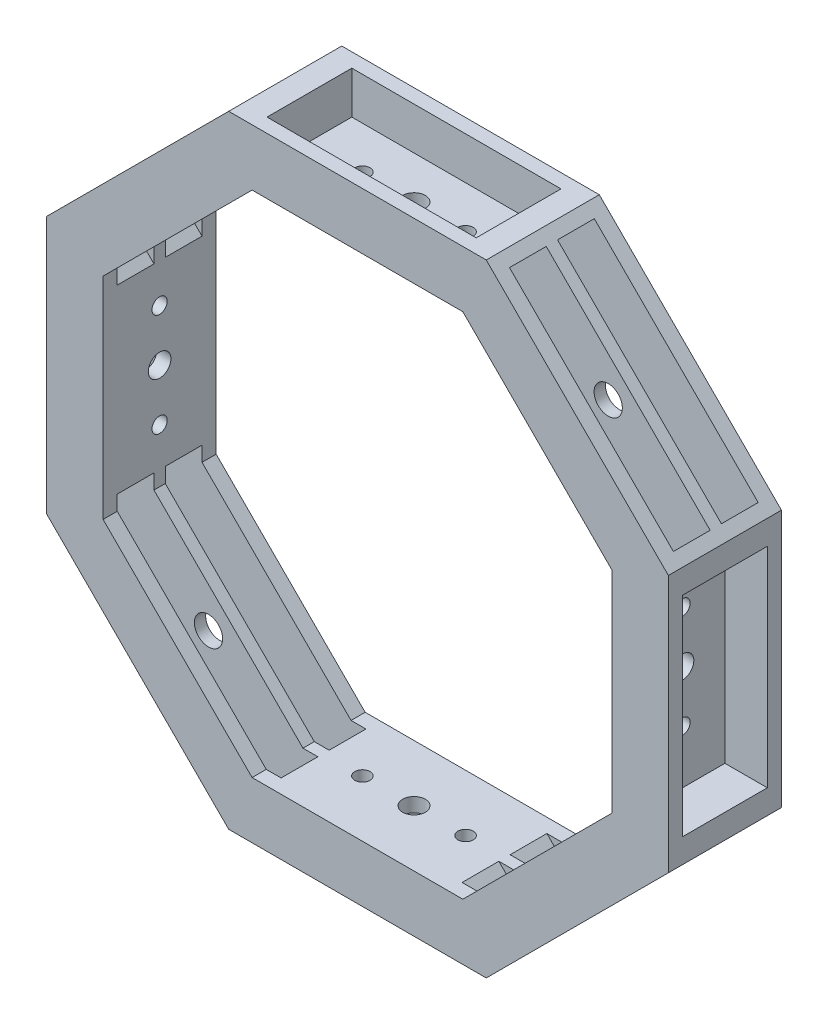
SolidWorks part; units mm, degrees
ref_plane "Plano frontal" through (0, 0, 0) normal (0, 0, 1) x (1, 0, 0)
ref_plane "Plano superior" through (0, 0, 0) normal (0, 1, 0) x (1, 0, 0)
ref_plane "Plano direito" through (0, 0, 0) normal (1, 0, 0) x (0, 0, -1)
sketch "Esboço1" plane through (0, 0, 0) normal (0, 0, 1) x (1, 0, 0)
  line L1 (110, 45.5635) -> (45.5635, 110)
  line L2 (45.5635, 110) -> (-45.5635, 110)
  line L3 (-45.5635, 110) -> (-110, 45.5635)
  line L4 (-110, 45.5635) -> (-110, -45.5635)
  line L5 (-110, -45.5635) -> (-45.5635, -110)
  line L6 (-45.5635, -110) -> (45.5635, -110)
  line L7 (45.5635, -110) -> (110, -45.5635)
  line L8 (110, -45.5635) -> (110, 45.5635)
  line L9 (90, 37.2792) -> (37.2792, 90)
  line L10 (37.2792, 90) -> (-37.2792, 90)
  line L11 (-37.2792, 90) -> (-90, 37.2792)
  line L12 (-90, 37.2792) -> (-90, -37.2792)
  line L13 (-90, -37.2792) -> (-37.2792, -90)
  line L14 (-37.2792, -90) -> (37.2792, -90)
  line L15 (37.2792, -90) -> (90, -37.2792)
  line L16 (90, -37.2792) -> (90, 37.2792)
  circle A0 centre (0, 0) radius 110 construction
  circle A1 centre (0, 0) radius 90 construction
extrude "Ressalto-extrusão1" add sketch "Esboço1" along normal blind 40
sketch "Esboço2" plane through (110, 0, 0) normal (1, 0, 0) x (0, 0, -1)
  line L13 (-5, 37) -> (-5, -37.0171)
  line L17 (-35, 37) -> (-35, -37.0171)
  line L19 (-5, -37.0171) -> (-5, -37)
  line L21 (-35, -37.0171) -> (-35, -37)
  line L25 (-35, -37) -> (-5, -37)
  line L29 (-35, 37) -> (-5, 37)
  circle A0 centre (-20, 0) radius 4
  circle A1 centre (-20, 18.25) radius 2.7
  circle A2 centre (-20, -18.25) radius 2.7
extrude "Corte-extrusão1" cut sketch "Esboço2" against normal blind 15 and the other way through all contours L29 L17 L21 L25 L19 L13 A2 A1 A0 region at (110, 0, 5.7985)
extrude "Corte-extrusão6" cut sketch "Esboço2<3>" against normal up to next contours A0 | A2 | A1 region at (110, 0, 20) region at (110, 18.25, 20) region at (110, -18.25, 20)
sketch "Esboço2<3>" plane through (110, 0, 0) normal (1, 0, 0) x (0, 0, -1) same geometry as "Esboço2"
sketch "Esboço3" plane through (0, 110, 0) normal (0, 1, 0) x (1, 0, 0)
  line L23 (37, -35) -> (-37.0171, -35)
  line L24 (37, -5) -> (-37.0171, -5)
  line L25 (-37.0171, -35) -> (-37, -35)
  line L26 (-37.0171, -5) -> (-37, -5)
  line L27 (-37, -5) -> (-37, -35)
  line L28 (37, -5) -> (37, -35)
  circle A0 centre (0, -20) radius 4
  circle A1 centre (18.25, -20) radius 2.7
  circle A2 centre (-18.25, -20) radius 2.7
extrude "Corte-extrusão2" cut sketch "Esboço3" against normal up to next contours A0 | A2 | A1 region at (0, 110, 20) region at (-18.25, 110, 20)
mirror "Espelhar1" about plane through (0, 0, 0) normal (1, 0, 0) of "Corte-extrusão1", "Corte-extrusão6"
extrude "Corte-extrusão7" cut sketch "Esboço3<3>" against normal blind 15 contours L28 L24 L27 L23 A2 A1 A0 region at (0, 110, 34.2015)
sketch "Esboço3<3>" plane through (0, 110, 0) normal (0, 1, 0) x (1, 0, 0) same geometry as "Esboço3"
mirror "Espelhar2" about plane through (0, 0, 0) normal (0, 1, 0) of "Corte-extrusão2", "Corte-extrusão7"
sketch "Esboço4" plane through (77.7817, 77.7817, 0) normal (0.7071, 0.7071, 0) x (0, 0, -1)
  line L2 (-35, 41) -> (-35, -41)
  line L4 (-5, 41) -> (-5, -41)
  line L8 (-35, -41) -> (-5, -41)
  line L12 (-35, 41) -> (-5, 41)
  line L14 (-20, 41) -> (-18, 41)
  line L16 (-20, -41) -> (-18, -41)
  line L17 (-18, 41) -> (-18, -41)
  line L18 (-20, -41) -> (-22, -41)
  line L20 (-20, 41) -> (-22, 41)
  line L21 (-22, -41) -> (-22, 41)
extrude "Corte-extrusão3" cut sketch "Esboço4" against normal up to next contours L12 L17 L8 L4 | L8 L21 L12 L2 region at (77.7817, 77.7817, 28.5) region at (77.7817, 77.7817, 11.5)
ref_plane "Plano1" through (0, 0, 0) normal (0.7071, 0.7071, 0) x (0.7071, -0.7071, 0)
mirror "Espelhar3" about plane through (0, 0, 0) normal (0.7071, 0.7071, 0) of "Corte-extrusão3"
ref_plane "Plano2" through (0, 0, 0) normal (0.7071, -0.7071, 0) x (-0.7071, -0.7071, 0)
sketch "Esboço9" plane through (77.7817, -77.7817, 0) normal (0.7071, -0.7071, 0) x (0, 0, -1)
  line L0 (-35, 41) -> (-35, -41)
  line L1 (-5, 41) -> (-5, -41)
  line L2 (-35, -41) -> (-5, -41)
  line L3 (-35, 41) -> (-5, 41)
  line L4 (-20, 41) -> (-18, 41)
  line L5 (-20, -41) -> (-18, -41)
  line L6 (-18, 41) -> (-18, -41)
  line L7 (-20, -41) -> (-22, -41)
  line L8 (-20, 41) -> (-22, 41)
  line L9 (-22, -41) -> (-22, 41)
extrude "Corte-extrusão8" cut sketch "Esboço9" against normal up to next contours L3 L6 L2 L1 | L2 L9 L3 L0 region at (77.7817, -77.7817, 28.5) region at (77.7817, -77.7817, 11.5)
mirror "Espelhar4" about plane through (0, 0, 0) normal (0.7071, -0.7071, 0) of "Corte-extrusão8"
sketch "Esboço10" plane through (0, 0, 40) normal (0, 0, 1) x (1, 0, 0)
  line L0 (0, 0) -> (0, -100) construction
  circle A0 centre (0, -100) radius 5
  circle A1 centre (-70.7107, -70.7107) radius 5
  circle A2 centre (-100, 0) radius 5 [skipped]
  circle A3 centre (-70.7107, 70.7107) radius 5
  circle A4 centre (0, 100) radius 5 [skipped]
  circle A5 centre (70.7107, 70.7107) radius 5
  circle A6 centre (100, 0) radius 5 [skipped]
  circle A7 centre (70.7107, -70.7107) radius 5
  dimension "D1" = 8
  dimension "D2" = 100
extrude "Corte-extrusão9" cut sketch "Esboço10" against normal up to next from surface starting at face at (-67.4767, -67.4767, 22)
